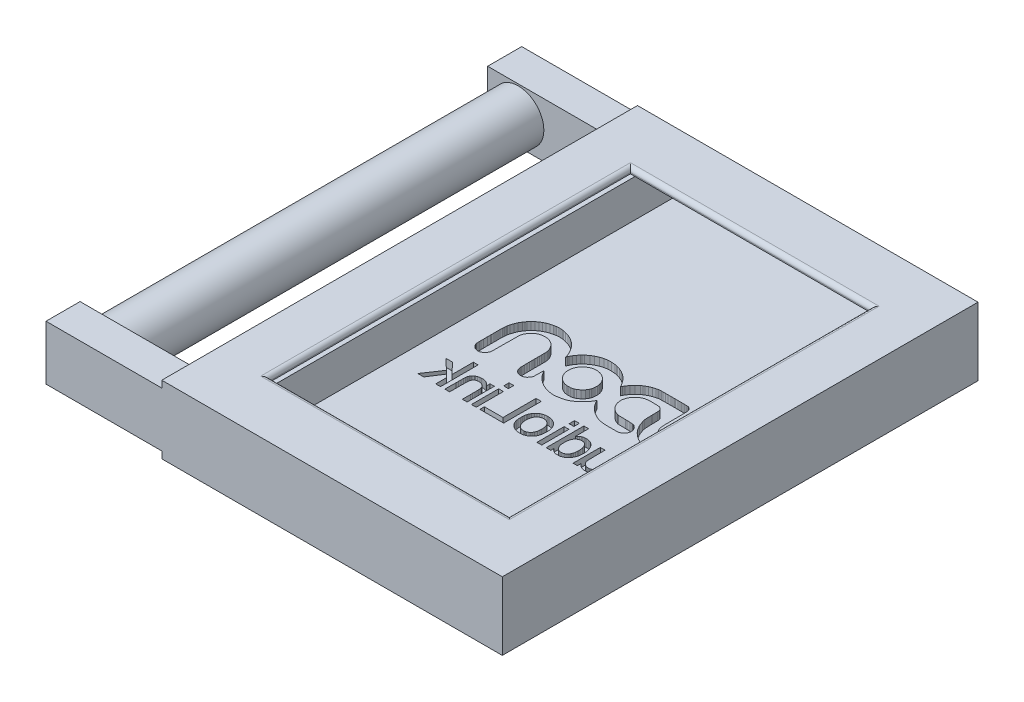
SolidWorks part; units mm, degrees
material "6061 Alloy"
ref_plane "Front" through (0, 0, 0) normal (0, 0, 1) x (1, 0, 0)
ref_plane "Top" through (0, 0, 0) normal (0, 1, 0) x (1, 0, 0)
ref_plane "Right" through (0, 0, 0) normal (1, 0, 0) x (0, 0, -1)
sketch "Sketch1" plane through (0, 0, 0) normal (0, 1, 0) x (1, 0, 0)
  line L1 (-100, -139.7) -> (100, -139.7)
  line L2 (-100, -139.7) -> (-100, 139.7)
  line L3 (-100, 139.7) -> (100, 139.7)
  line L4 (100, -139.7) -> (100, 139.7)
  line L5 (-100, -139.7) -> (100, 139.7) construction
  line L6 (-100, 139.7) -> (100, -139.7) construction
  point P0 (0, 0)
  dimension "D1" = 279.4
  dimension "D2" = 200
extrude "Boss-Extrude1" add sketch "Sketch1" along normal mid plane 40
sketch "Sketch2" plane through (0, 0, 0) normal (0, 1, 0) x (1, 0, 0)
  line L1 (-100, 139.7) -> (-168, 139.7)
  line L2 (-100, 139.7) -> (-100, 119.7)
  line L3 (-100, 119.7) -> (-168, 119.7)
  line L4 (-168, 139.7) -> (-168, 119.7)
  dimension "D1" = 68
  dimension "D2" = 20
extrude "Boss-Extrude2" add sketch "Sketch2" along normal mid plane 32
sketch "Sketch3" plane through (0, 0, 0) normal (0, 0, 1) x (1, 0, 0)
  circle A0 centre (-150, 0) radius 15
  point P2 (0, 0)
  dimension "D1" = 30
  dimension "D2" = 150
extrude "Boss-Extrude3" add sketch "Sketch3" against normal up to surface (119.7 mm away) up to face at (-134, 0, -119.7)
mirror "Mirror1" about plane through (0, 0, 0) normal (0, 0, 1) of "Boss-Extrude2", "Boss-Extrude3"
sketch "Sketch4" plane through (0, 20, 0) normal (0, 1, 0) x (1, 0, 0)
  line L1 (-70.485, -106.045) -> (70.485, -106.045)
  line L2 (-70.485, -106.045) -> (-70.485, 106.045)
  line L3 (-70.485, 106.045) -> (70.485, 106.045)
  line L4 (70.485, -106.045) -> (70.485, 106.045)
  line L5 (-70.485, -106.045) -> (70.485, 106.045) construction
  line L6 (-70.485, 106.045) -> (70.485, -106.045) construction
  point P0 (0, 0)
  dimension "D1" = 212.09
  dimension "D2" = 140.97
extrude "Cut-Extrude1" cut sketch "Sketch4" against normal blind 6.35
sketch "Sketch5" plane through (0, 0, 139.7) normal (0, 0, 1) x (1, 0, 0)
  line L0 (70.485, 13.65) -> (70.485, 20) construction
  line L1 (-87.249, 16.825) -> (87.249, 16.825)
  line L2 (-87.249, 16.825) -> (-87.249, 8.443)
  line L3 (-87.249, 8.443) -> (87.249, 8.443)
  line L4 (87.249, 16.825) -> (87.249, 8.443)
  line L5 (-87.249, 16.825) -> (87.249, 8.443) construction
  line L6 (-87.249, 8.443) -> (87.249, 16.825) construction
  line L7 (-70.485, 13.65) -> (-70.485, 20) construction
  line L8 (70.485, 13.65) -> (70.485, 20) construction
  line L9 (-70.485, 13.65) -> (-70.485, 20) construction
  line L10 (-100, 20) -> (100, 20) construction
  point P0 (0, 12.634)
  dimension "D1" = 8.382
  dimension "D2" = 3.175
  dimension "D3" = 16.764
  dimension "D4" = 16.764
extrude "Cut-Extrude2" cut sketch "Sketch5" along normal offset from surface (262.509 mm away) 16.764 from surface up to face at (0, 16.825, 106.045) offset beyond the face yes starting at face at (-67, 0, -139.7)
fillet "Fillet1" radius 2.54 4 edges at (0, 20, 106.045) (70.485, 20, 0) (-70.485, 20, 0) (0, 20, -106.045)
sketch "Sketch6" plane through (0, 0, -139.7) normal (0, 0, -1) x (-1, 0, 0)
  line L0 (87.249, 8.443) -> (-87.249, 8.443) construction
  line L1 (-76.2, -13.65) -> (76.2, -13.65)
  line L2 (-76.2, -13.65) -> (-76.2, 8.443)
  line L3 (-76.2, 8.443) -> (76.2, 8.443)
  line L4 (76.2, -13.65) -> (76.2, 8.443)
  line L5 (-76.2, -13.65) -> (76.2, 8.443) construction
  line L6 (-76.2, 8.443) -> (76.2, -13.65) construction
  line L7 (-100, -20) -> (100, -20) construction
  point P0 (0, -2.6035)
  point P7 (0, 0)
  dimension "D1" = 152.4
  dimension "D2" = 6.35
extrude "Cut-Extrude3" cut sketch "Sketch6" against normal up to surface (262.509 mm away) up to face at (0, 12.634, 122.809)
sketch "Sketch9" plane through (0, -20, 0) normal (0, -1, 0) x (1, 0, 0)
  line L0 (47.93, -1.8124) -> (48.8593, -2.019)
  line L1 (48.8593, -2.019) -> (50.5205, -2.4998)
  line L2 (50.5205, -2.4998) -> (52.0185, -3.112)
  line L3 (52.0185, -3.112) -> (53.4733, -3.9044)
  line L4 (53.4733, -3.9044) -> (54.222, -4.3835)
  line L5 (54.222, -4.3835) -> (54.8334, -4.8153)
  line L6 (54.8334, -4.8153) -> (56.0096, -5.784)
  line L7 (56.0096, -5.784) -> (57.1117, -6.8762)
  line L8 (57.1117, -6.8762) -> (58.1253, -8.0714)
  line L9 (58.1253, -8.0714) -> (59.0359, -9.3494)
  line L10 (59.0359, -9.3494) -> (59.829, -10.6898)
  line L11 (59.829, -10.6898) -> (60.49, -12.0723)
  line L12 (60.49, -12.0723) -> (61.0045, -13.4765)
  line L13 (61.0045, -13.4765) -> (61.2023, -14.1804)
  line L14 (61.2023, -14.1804) -> (61.4, -15.0085)
  line L15 (61.4, -15.0085) -> (61.6145, -16.1928)
  line L16 (61.6145, -16.1928) -> (61.7109, -17.0783)
  line L17 (61.7109, -17.0783) -> (61.7768, -18.1482)
  line L18 (61.7768, -18.1482) -> (61.8178, -19.4948)
  line L19 (61.8178, -19.4948) -> (61.8396, -21.2101)
  line L20 (61.8396, -21.2101) -> (61.8467, -22.7941)
  line L21 (61.8467, -22.7941) -> (61.8484, -24.0134)
  line L22 (61.8484, -24.0134) -> (61.8486, -24.6763)
  line L23 (61.8486, -24.6763) -> (61.8486, -25.2604)
  line L24 (61.8486, -25.2604) -> (61.8482, -26.327)
  line L25 (61.8482, -26.327) -> (61.846, -27.691)
  line L26 (61.846, -27.691) -> (61.8385, -29.1187)
  line L27 (61.8385, -29.1187) -> (61.8233, -30.1692)
  line L28 (61.8233, -30.1692) -> (61.798, -30.9181)
  line L29 (61.798, -30.9181) -> (61.7599, -31.4412)
  line L30 (61.7599, -31.4412) -> (61.6732, -31.9679)
  line L31 (61.6732, -31.9679) -> (61.5921, -32.2575)
  line L32 (61.5921, -32.2575) -> (61.4441, -32.651)
  line L33 (61.4441, -32.651) -> (61.0089, -33.4052)
  line L34 (61.0089, -33.4052) -> (60.4202, -34.0791)
  line L35 (60.4202, -34.0791) -> (59.7166, -34.6283)
  line L36 (59.7166, -34.6283) -> (59.3337, -34.8425)
  line L37 (59.3337, -34.8425) -> (58.9346, -35.0064)
  line L38 (58.9346, -35.0064) -> (58.0614, -35.1964)
  line L39 (58.0614, -35.1964) -> (57.1488, -35.2022)
  line L40 (57.1488, -35.2022) -> (56.2694, -35.0232)
  line L41 (56.2694, -35.0232) -> (55.8648, -34.8643)
  line L42 (55.8648, -34.8643) -> (55.3692, -34.5995)
  line L43 (55.3692, -34.5995) -> (54.5302, -33.9483)
  line L44 (54.5302, -33.9483) -> (53.8984, -33.1408)
  line L45 (53.8984, -33.1408) -> (53.4792, -32.1837)
  line L46 (53.4792, -32.1837) -> (53.351, -31.6514)
  line L47 (53.351, -31.6514) -> (53.3349, -31.5347)
  line L48 (53.3349, -31.5347) -> (53.3054, -31.1451)
  line L49 (53.3054, -31.1451) -> (53.2796, -30.5535)
  line L50 (53.2796, -30.5535) -> (53.2577, -29.7676)
  line L51 (53.2577, -29.7676) -> (53.2397, -28.795)
  line L52 (53.2397, -28.795) -> (53.2258, -27.6434)
  line L53 (53.2258, -27.6434) -> (53.2161, -26.3204)
  line L54 (53.2161, -26.3204) -> (53.2108, -24.8337)
  line L55 (53.2108, -24.8337) -> (53.2099, -24.0314)
  line L56 (53.2099, -24.0314) -> (53.2069, -22.5476)
  line L57 (53.2069, -22.5476) -> (53.1942, -20.5567)
  line L58 (53.1942, -20.5567) -> (53.1807, -19.4123)
  line L59 (53.1807, -19.4123) -> (53.1636, -18.4351)
  line L60 (53.1636, -18.4351) -> (53.1432, -17.6434)
  line L61 (53.1432, -17.6434) -> (53.1198, -17.055)
  line L62 (53.1198, -17.055) -> (53.0937, -16.6882)
  line L63 (53.0937, -16.6882) -> (53.0797, -16.5934)
  line L64 (53.0797, -16.5934) -> (52.8926, -15.8966)
  line L65 (52.8926, -15.8966) -> (52.3521, -14.5891)
  line L66 (52.3521, -14.5891) -> (51.6095, -13.4123)
  line L67 (51.6095, -13.4123) -> (50.6885, -12.385)
  line L68 (50.6885, -12.385) -> (49.6127, -11.5261)
  line L69 (49.6127, -11.5261) -> (48.4057, -10.8544)
  line L70 (48.4057, -10.8544) -> (47.0912, -10.3889)
  line L71 (47.0912, -10.3889) -> (45.6927, -10.1483)
  line L72 (45.6927, -10.1483) -> (44.9694, -10.1183)
  line L73 (44.9694, -10.1183) -> (43.9951, -10.1684)
  line L74 (43.9951, -10.1684) -> (42.185, -10.5837)
  line L75 (42.185, -10.5837) -> (41.2769, -10.9654)
  line L76 (41.2769, -10.9654) -> (40.8053, -11.229)
  line L77 (40.8053, -11.229) -> (39.795, -11.9878)
  line L78 (39.795, -11.9878) -> (38.8185, -12.936)
  line L79 (38.8185, -12.936) -> (38.0234, -13.93)
  line L80 (38.0234, -13.93) -> (37.7401, -14.3995)
  line L81 (37.7401, -14.3995) -> (37.5607, -14.7386)
  line L82 (37.5607, -14.7386) -> (37.2712, -15.3057)
  line L83 (37.2712, -15.3057) -> (37.0622, -15.844)
  line L84 (37.0622, -15.844) -> (36.9192, -16.4977)
  line L85 (36.9192, -16.4977) -> (36.8279, -17.4103)
  line L86 (36.8279, -17.4103) -> (36.7846, -18.3514)
  line L87 (36.7846, -18.3514) -> (36.7643, -19.1346)
  line L88 (36.7643, -19.1346) -> (36.7489, -20.0635)
  line L89 (36.7489, -20.0635) -> (36.7365, -21.1561)
  line L90 (36.7365, -21.1561) -> (36.7253, -22.4303)
  line L91 (36.7253, -22.4303) -> (36.7135, -23.9041)
  line L92 (36.7135, -23.9041) -> (36.7068, -24.7214)
  line L93 (36.7068, -24.7214) -> (36.7002, -25.5284)
  line L94 (36.7002, -25.5284) -> (36.6881, -26.9863)
  line L95 (36.6881, -26.9863) -> (36.6766, -28.2491)
  line L96 (36.6766, -28.2491) -> (36.664, -29.3326)
  line L97 (36.664, -29.3326) -> (36.6488, -30.2526)
  line L98 (36.6488, -30.2526) -> (36.6297, -31.0248)
  line L99 (36.6297, -31.0248) -> (36.5902, -31.9403)
  line L100 (36.5902, -31.9403) -> (36.5095, -32.7906)
  line L101 (36.5095, -32.7906) -> (36.3858, -33.3329)
  line L102 (36.3858, -33.3329) -> (36.0936, -33.8445)
  line L103 (36.0936, -33.8445) -> (35.8102, -34.1679)
  line L104 (35.8102, -34.1679) -> (35.3632, -34.5848)
  line L105 (35.3632, -34.5848) -> (34.8735, -34.9207)
  line L106 (34.8735, -34.9207) -> (34.6857, -35.0125)
  line L107 (34.6857, -35.0125) -> (34.2701, -35.1085)
  line L108 (34.2701, -35.1085) -> (33.7539, -35.1494)
  line L109 (33.7539, -35.1494) -> (32.9267, -35.1756)
  line L110 (32.9267, -35.1756) -> (32.0403, -35.1876)
  line L111 (32.0403, -35.1876) -> (31.2987, -35.1927)
  line L112 (31.2987, -35.1927) -> (30.4215, -35.196)
  line L113 (30.4215, -35.196) -> (29.3959, -35.1979)
  line L114 (29.3959, -35.1979) -> (28.2091, -35.1987)
  line L115 (28.2091, -35.1987) -> (26.8482, -35.1989)
  line L116 (26.8482, -35.1989) -> (26.0985, -35.1989)
  line L117 (26.0985, -35.1989) -> (25.4237, -35.1989)
  line L118 (25.4237, -35.1989) -> (24.1823, -35.1982)
  line L119 (24.1823, -35.1982) -> (22.573, -35.1954)
  line L120 (22.573, -35.1954) -> (20.8496, -35.1874)
  line L121 (20.8496, -35.1874) -> (19.5398, -35.1726)
  line L122 (19.5398, -35.1726) -> (18.5682, -35.1492)
  line L123 (18.5682, -35.1492) -> (17.8592, -35.1155)
  line L124 (17.8592, -35.1155) -> (17.1232, -35.0417)
  line L125 (17.1232, -35.0417) -> (16.7409, -34.9742)
  line L126 (16.7409, -34.9742) -> (15.8881, -34.7797)
  line L127 (15.8881, -34.7797) -> (14.2327, -34.2776)
  line L128 (14.2327, -34.2776) -> (12.6521, -33.628)
  line L129 (12.6521, -33.628) -> (11.1562, -32.8348)
  line L130 (11.1562, -32.8348) -> (10.443, -32.3856)
  line L131 (10.443, -32.3856) -> (9.6232, -31.7926)
  line L132 (9.6232, -31.7926) -> (8.0064, -30.3585)
  line L133 (8.0064, -30.3585) -> (6.5288, -28.7146)
  line L134 (6.5288, -28.7146) -> (5.3208, -27.006)
  line L135 (5.3208, -27.006) -> (4.8587, -26.1729)
  line L136 (4.8587, -26.1729) -> (4.4117, -25.2748)
  line L137 (4.4117, -25.2748) -> (3.998, -26.0686)
  line L138 (3.998, -26.0686) -> (3.5333, -26.9017)
  line L139 (3.5333, -26.9017) -> (2.4731, -28.475)
  line L140 (2.4731, -28.475) -> (1.2523, -29.914)
  line L141 (1.2523, -29.914) -> (-0.1132, -31.2064)
  line L142 (-0.1132, -31.2064) -> (-1.607, -32.34)
  line L143 (-1.607, -32.34) -> (-3.2132, -33.3026)
  line L144 (-3.2132, -33.3026) -> (-4.9154, -34.0818)
  line L145 (-4.9154, -34.0818) -> (-6.6976, -34.6655)
  line L146 (-6.6976, -34.6655) -> (-7.6137, -34.8801)
  line L147 (-7.6137, -34.8801) -> (-8.6686, -35.0616)
  line L148 (-8.6686, -35.0616) -> (-10.7713, -35.2252)
  line L149 (-10.7713, -35.2252) -> (-12.8491, -35.1279)
  line L150 (-12.8491, -35.1279) -> (-14.8833, -34.7755)
  line L151 (-14.8833, -34.7755) -> (-16.8553, -34.1736)
  line L152 (-16.8553, -34.1736) -> (-18.7463, -33.3279)
  line L153 (-18.7463, -33.3279) -> (-20.5378, -32.2442)
  line L154 (-20.5378, -32.2442) -> (-22.2109, -30.9281)
  line L155 (-22.2109, -30.9281) -> (-22.9973, -30.1847)
  line L156 (-22.9973, -30.1847) -> (-23.5248, -29.6247)
  line L157 (-23.5248, -29.6247) -> (-24.5397, -28.3737)
  line L158 (-24.5397, -28.3737) -> (-25.4499, -27.0237)
  line L159 (-25.4499, -27.0237) -> (-26.1944, -25.6654)
  line L160 (-26.1944, -25.6654) -> (-26.4854, -25.0115)
  line L161 (-26.4854, -25.0115) -> (-26.7632, -24.328)
  line L162 (-26.7632, -24.328) -> (-27.0924, -25.382)
  line L163 (-27.0924, -25.382) -> (-27.4778, -26.465)
  line L164 (-27.4778, -26.465) -> (-28.506, -28.5948)
  line L165 (-28.506, -28.5948) -> (-29.8176, -30.5858)
  line L166 (-29.8176, -30.5858) -> (-31.3414, -32.3296)
  line L167 (-31.3414, -32.3296) -> (-32.1605, -33.075)
  line L168 (-32.1605, -33.075) -> (-33.1539, -33.8619)
  line L169 (-33.1539, -33.8619) -> (-35.1274, -35.1509)
  line L170 (-35.1274, -35.1509) -> (-37.1834, -36.1065)
  line L171 (-37.1834, -36.1065) -> (-39.442, -36.7846)
  line L172 (-39.442, -36.7846) -> (-40.6848, -37.0371)
  line L173 (-40.6848, -37.0371) -> (-41.3523, -37.1437)
  line L174 (-41.3523, -37.1437) -> (-42.5862, -37.2657)
  line L175 (-42.5862, -37.2657) -> (-43.7685, -37.2661)
  line L176 (-43.7685, -37.2661) -> (-44.9993, -37.1451)
  line L177 (-44.9993, -37.1451) -> (-45.6641, -37.0391)
  line L178 (-45.6641, -37.0391) -> (-46.5297, -36.868)
  line L179 (-46.5297, -36.868) -> (-48.1852, -36.4278)
  line L180 (-48.1852, -36.4278) -> (-49.7428, -35.8549)
  line L181 (-49.7428, -35.8549) -> (-51.2063, -35.1471)
  line L182 (-51.2063, -35.1471) -> (-52.5794, -34.302)
  line L183 (-52.5794, -34.302) -> (-53.8658, -33.3174)
  line L184 (-53.8658, -33.3174) -> (-55.0694, -32.1909)
  line L185 (-55.0694, -32.1909) -> (-56.1937, -30.9202)
  line L186 (-56.1937, -30.9202) -> (-56.7274, -30.2301)
  line L187 (-56.7274, -30.2301) -> (-57.2616, -29.4642)
  line L188 (-57.2616, -29.4642) -> (-58.1905, -27.8525)
  line L189 (-58.1905, -27.8525) -> (-58.9425, -26.1127)
  line L190 (-58.9425, -26.1127) -> (-59.5287, -24.2193)
  line L191 (-59.5287, -24.2193) -> (-59.7631, -23.2069)
  line L192 (-59.7631, -23.2069) -> (-59.8639, -22.7055)
  line L193 (-59.8639, -22.7055) -> (-59.9693, -21.9562)
  line L194 (-59.9693, -21.9562) -> (-60.0143, -21.2913)
  line L195 (-60.0143, -21.2913) -> (-60.0433, -20.3602)
  line L196 (-60.0433, -20.3602) -> (-60.0598, -19.0481)
  line L197 (-60.0598, -19.0481) -> (-60.0662, -17.7451)
  line L198 (-60.0662, -17.7451) -> (-60.0684, -16.6976)
  line L199 (-60.0684, -16.6976) -> (-60.0695, -15.4904)
  line L200 (-60.0695, -15.4904) -> (-60.0699, -14.109)
  line L201 (-60.0699, -14.109) -> (-60.07, -13.3486)
  line L202 (-60.07, -13.3486) -> (-60.0679, -11.6508)
  line L203 (-60.0679, -11.6508) -> (-60.057, -9.3283)
  line L204 (-60.057, -9.3283) -> (-60.0452, -7.9785)
  line L205 (-60.0452, -7.9785) -> (-60.0302, -6.8266)
  line L206 (-60.0302, -6.8266) -> (-60.0125, -5.9063)
  line L207 (-60.0125, -5.9063) -> (-59.9926, -5.2512)
  line L208 (-59.9926, -5.2512) -> (-59.9708, -4.8951)
  line L209 (-59.9708, -4.8951) -> (-59.9593, -4.8396)
  line L210 (-59.9593, -4.8396) -> (-59.9043, -4.756)
  line L211 (-59.9043, -4.756) -> (-59.7656, -4.4437)
  line L212 (-59.7656, -4.4437) -> (-59.699, -4.2534)
  line L213 (-59.699, -4.2534) -> (-59.6021, -4.0237)
  line L214 (-59.6021, -4.0237) -> (-59.2623, -3.4944)
  line L215 (-59.2623, -3.4944) -> (-58.5336, -2.6951)
  line L216 (-58.5336, -2.6951) -> (-58.0151, -2.2908)
  line L217 (-58.0151, -2.2908) -> (-57.7273, -2.1311)
  line L218 (-57.7273, -2.1311) -> (-57.055, -1.8689)
  line L219 (-57.055, -1.8689) -> (-56.3263, -1.7002)
  line L220 (-56.3263, -1.7002) -> (-55.6278, -1.6448)
  line L221 (-55.6278, -1.6448) -> (-55.3171, -1.666)
  line L222 (-55.3171, -1.666) -> (-54.7785, -1.7767)
  line L223 (-54.7785, -1.7767) -> (-53.7585, -2.2139)
  line L224 (-53.7585, -2.2139) -> (-52.8596, -2.9046)
  line L225 (-52.8596, -2.9046) -> (-52.136, -3.807)
  line L226 (-52.136, -3.807) -> (-51.8568, -4.3246)
  line L227 (-51.8568, -4.3246) -> (-51.4985, -5.0999)
  line L228 (-51.4985, -5.0999) -> (-51.4312, -13.6724)
  line L229 (-51.4312, -13.6724) -> (-51.4252, -14.4369)
  line L230 (-51.4252, -14.4369) -> (-51.4139, -15.8277)
  line L231 (-51.4139, -15.8277) -> (-51.4034, -17.0448)
  line L232 (-51.4034, -17.0448) -> (-51.393, -18.101)
  line L233 (-51.393, -18.101) -> (-51.3824, -19.0094)
  line L234 (-51.3824, -19.0094) -> (-51.371, -19.7826)
  line L235 (-51.371, -19.7826) -> (-51.3516, -20.7173)
  line L236 (-51.3516, -20.7173) -> (-51.3186, -21.6106)
  line L237 (-51.3186, -21.6106) -> (-51.2741, -22.1949)
  line L238 (-51.2741, -22.1949) -> (-51.1775, -22.7169)
  line L239 (-51.1775, -22.7169) -> (-51.0877, -22.9784)
  line L240 (-51.0877, -22.9784) -> (-50.776, -23.7156)
  line L241 (-50.776, -23.7156) -> (-49.9983, -25.0764)
  line L242 (-49.9983, -25.0764) -> (-49.0459, -26.2477)
  line L243 (-49.0459, -26.2477) -> (-47.9559, -27.1837)
  line L244 (-47.9559, -27.1837) -> (-47.371, -27.5492)
  line L245 (-47.371, -27.5492) -> (-46.8306, -27.8335)
  line L246 (-46.8306, -27.8335) -> (-45.853, -28.2463)
  line L247 (-45.853, -28.2463) -> (-44.8852, -28.4825)
  line L248 (-44.8852, -28.4825) -> (-43.7739, -28.5794)
  line L249 (-43.7739, -28.5794) -> (-43.1165, -28.5874)
  line L250 (-43.1165, -28.5874) -> (-42.6016, -28.5831)
  line L251 (-42.6016, -28.5831) -> (-41.8473, -28.5534)
  line L252 (-41.8473, -28.5534) -> (-41.2968, -28.4714)
  line L253 (-41.2968, -28.4714) -> (-40.7543, -28.3077)
  line L254 (-40.7543, -28.3077) -> (-40.4247, -28.186)
  line L255 (-40.4247, -28.186) -> (-39.9657, -27.9967)
  line L256 (-39.9657, -27.9967) -> (-39.0406, -27.5409)
  line L257 (-39.0406, -27.5409) -> (-38.6885, -27.3306)
  line L258 (-38.6885, -27.3306) -> (-38.2703, -27.0276)
  line L259 (-38.2703, -27.0276) -> (-37.4493, -26.2898)
  line L260 (-37.4493, -26.2898) -> (-36.6972, -25.4315)
  line L261 (-36.6972, -25.4315) -> (-36.0723, -24.5191)
  line L262 (-36.0723, -24.5191) -> (-35.8257, -24.0634)
  line L263 (-35.8257, -24.0634) -> (-35.5228, -23.4356)
  line L264 (-35.5228, -23.4356) -> (-35.2091, -22.5816)
  line L265 (-35.2091, -22.5816) -> (-35.0772, -21.8826)
  line L266 (-35.0772, -21.8826) -> (-34.9942, -20.9297)
  line L267 (-34.9942, -20.9297) -> (-34.9571, -19.9706)
  line L268 (-34.9571, -19.9706) -> (-34.9417, -19.1848)
  line L269 (-34.9417, -19.1848) -> (-34.9322, -18.2629)
  line L270 (-34.9322, -18.2629) -> (-34.9272, -17.1889)
  line L271 (-34.9272, -17.1889) -> (-34.9253, -15.9467)
  line L272 (-34.9253, -15.9467) -> (-34.925, -14.52)
  line L273 (-34.925, -14.52) -> (-34.925, -13.7326)
  line L274 (-34.925, -13.7326) -> (-34.9244, -12.8119)
  line L275 (-34.9244, -12.8119) -> (-34.9199, -11.1176)
  line L276 (-34.9199, -11.1176) -> (-34.911, -9.6236)
  line L277 (-34.911, -9.6236) -> (-34.8978, -8.335)
  line L278 (-34.8978, -8.335) -> (-34.8803, -7.2571)
  line L279 (-34.8803, -7.2571) -> (-34.8587, -6.3951)
  line L280 (-34.8587, -6.3951) -> (-34.833, -5.7541)
  line L281 (-34.833, -5.7541) -> (-34.8033, -5.3394)
  line L282 (-34.8033, -5.3394) -> (-34.787, -5.2185)
  line L283 (-34.787, -5.2185) -> (-34.6999, -4.8323)
  line L284 (-34.6999, -4.8323) -> (-34.4399, -4.1124)
  line L285 (-34.4399, -4.1124) -> (-34.0739, -3.4695)
  line L286 (-34.0739, -3.4695) -> (-33.6116, -2.9118)
  line L287 (-33.6116, -2.9118) -> (-33.063, -2.4477)
  line L288 (-33.063, -2.4477) -> (-32.4378, -2.0856)
  line L289 (-32.4378, -2.0856) -> (-31.746, -1.8338)
  line L290 (-31.746, -1.8338) -> (-30.9973, -1.7005)
  line L291 (-30.9973, -1.7005) -> (-30.6047, -1.681)
  line L292 (-30.6047, -1.681) -> (-29.981, -1.7185)
  line L293 (-29.981, -1.7185) -> (-28.8386, -2.046)
  line L294 (-28.8386, -2.046) -> (-27.851, -2.7004)
  line L295 (-27.851, -2.7004) -> (-27.0358, -3.6702)
  line L296 (-27.0358, -3.6702) -> (-26.6984, -4.2697)
  line L297 (-26.6984, -4.2697) -> (-26.585, -4.5073)
  line L298 (-26.585, -4.5073) -> (-26.4362, -4.9681)
  line L299 (-26.4362, -4.9681) -> (-26.3751, -5.4722)
  line L300 (-26.3751, -5.4722) -> (-26.3502, -5.9652)
  line L301 (-26.3502, -5.9652) -> (-26.3328, -6.6345)
  line L302 (-26.3328, -6.6345) -> (-26.3184, -7.5234)
  line L303 (-26.3184, -7.5234) -> (-26.3109, -8.0637)
  line L304 (-26.3109, -8.0637) -> (-26.2689, -11.1546)
  line L305 (-26.2689, -11.1546) -> (-25.7104, -10.1744)
  line L306 (-25.7104, -10.1744) -> (-25.2365, -9.3917)
  line L307 (-25.2365, -9.3917) -> (-24.177, -7.917)
  line L308 (-24.177, -7.917) -> (-22.9796, -6.5718)
  line L309 (-22.9796, -6.5718) -> (-21.6581, -5.3662)
  line L310 (-21.6581, -5.3662) -> (-20.2262, -4.3101)
  line L311 (-20.2262, -4.3101) -> (-18.6974, -3.4138)
  line L312 (-18.6974, -3.4138) -> (-17.0854, -2.6873)
  line L313 (-17.0854, -2.6873) -> (-15.404, -2.1406)
  line L314 (-15.404, -2.1406) -> (-14.5415, -1.9379)
  line L315 (-14.5415, -1.9379) -> (-14.0986, -1.847)
  line L316 (-14.0986, -1.847) -> (-13.2307, -1.6695)
  line L317 (-13.2307, -1.6695) -> (-12.9126, -1.6047)
  line L318 (-12.9126, -1.6047) -> (-12.466, -1.5337)
  line L319 (-12.466, -1.5337) -> (-11.4389, -1.475)
  line L320 (-11.4389, -1.475) -> (-9.655, -1.5789)
  line L321 (-9.655, -1.5789) -> (-7.0806, -2.0304)
  line L322 (-7.0806, -2.0304) -> (-5.2179, -2.5662)
  line L323 (-5.2179, -2.5662) -> (-4.1006, -3.001)
  line L324 (-4.1006, -3.001) -> (-3.5977, -3.2385)
  line L325 (-3.5977, -3.2385) -> (-2.4454, -3.8854)
  line L326 (-2.4454, -3.8854) -> (-0.2515, -5.484)
  line L327 (-0.2515, -5.484) -> (1.7045, -7.4005)
  line L328 (1.7045, -7.4005) -> (3.3142, -9.5288)
  line L329 (3.3142, -9.5288) -> (3.9552, -10.6392)
  line L330 (3.9552, -10.6392) -> (4.3904, -11.4794)
  line L331 (4.3904, -11.4794) -> (4.9413, -10.4279)
  line L332 (4.9413, -10.4279) -> (5.3263, -9.7401)
  line L333 (5.3263, -9.7401) -> (6.2161, -8.4126)
  line L334 (6.2161, -8.4126) -> (7.2502, -7.1614)
  line L335 (7.2502, -7.1614) -> (8.4106, -6.0016)
  line L336 (8.4106, -6.0016) -> (9.6792, -4.9484)
  line L337 (9.6792, -4.9484) -> (11.0377, -4.0168)
  line L338 (11.0377, -4.0168) -> (12.468, -3.2219)
  line L339 (12.468, -3.2219) -> (13.9519, -2.5787)
  line L340 (13.9519, -2.5787) -> (14.7084, -2.3187)
  line L341 (14.7084, -2.3187) -> (15.5331, -2.0749)
  line L342 (15.5331, -2.0749) -> (17.1024, -1.7339)
  line L343 (17.1024, -1.7339) -> (18.4035, -1.5869)
  line L344 (18.4035, -1.5869) -> (19.4225, -1.5316)
  line L345 (19.4225, -1.5316) -> (20.6203, -1.5047)
  line L346 (20.6203, -1.5047) -> (22.0461, -1.5013)
  line L347 (22.0461, -1.5013) -> (22.86, -1.5068)
  line L348 (22.86, -1.5068) -> (26.9875, -1.5439)
  line L349 (26.9875, -1.5439) -> (27.7793, -1.9096)
  line L350 (27.7793, -1.9096) -> (28.2315, -2.1493)
  line L351 (28.2315, -2.1493) -> (29.0123, -2.7454)
  line L352 (29.0123, -2.7454) -> (29.621, -3.4699)
  line L353 (29.621, -3.4699) -> (30.0487, -4.2897)
  line L354 (30.0487, -4.2897) -> (30.2865, -5.172)
  line L355 (30.2865, -5.172) -> (30.3255, -6.0836)
  line L356 (30.3255, -6.0836) -> (30.1568, -6.9916)
  line L357 (30.1568, -6.9916) -> (29.7716, -7.8632)
  line L358 (29.7716, -7.8632) -> (29.495, -8.2749)
  line L359 (29.495, -8.2749) -> (29.0358, -8.7861)
  line L360 (29.0358, -8.7861) -> (27.8992, -9.6272)
  line L361 (27.8992, -9.6272) -> (27.3275, -9.8789)
  line L362 (27.3275, -9.8789) -> (27.2543, -9.8968)
  line L363 (27.2543, -9.8968) -> (27.0073, -9.9317)
  line L364 (27.0073, -9.9317) -> (26.3933, -9.981)
  line L365 (26.3933, -9.981) -> (25.1434, -10.0404)
  line L366 (25.1434, -10.0404) -> (23.4327, -10.0907)
  line L367 (23.4327, -10.0907) -> (22.4155, -10.1121)
  line L368 (22.4155, -10.1121) -> (17.9705, -10.1949)
  line L369 (17.9705, -10.1949) -> (17.0207, -10.5531)
  line L370 (17.0207, -10.5531) -> (16.3324, -10.846)
  line L371 (16.3324, -10.846) -> (15.0675, -11.5821)
  line L372 (15.0675, -11.5821) -> (13.9649, -12.4963)
  line L373 (13.9649, -12.4963) -> (13.0414, -13.5613)
  line L374 (13.0414, -13.5613) -> (12.3136, -14.7502)
  line L375 (12.3136, -14.7502) -> (11.7978, -16.0359)
  line L376 (11.7978, -16.0359) -> (11.5108, -17.3913)
  line L377 (11.5108, -17.3913) -> (11.4692, -18.7893)
  line L378 (11.4692, -18.7893) -> (11.5455, -19.4959)
  line L379 (11.5455, -19.4959) -> (11.6767, -20.1945)
  line L380 (11.6767, -20.1945) -> (12.0623, -21.4564)
  line L381 (12.0623, -21.4564) -> (12.6362, -22.5846)
  line L382 (12.6362, -22.5846) -> (13.4271, -23.6357)
  line L383 (13.4271, -23.6357) -> (13.9129, -24.1499)
  line L384 (13.9129, -24.1499) -> (14.2939, -24.5126)
  line L385 (14.2939, -24.5126) -> (15.0462, -25.1282)
  line L386 (15.0462, -25.1282) -> (16.2354, -25.8314)
  line L387 (16.2354, -25.8314) -> (17.1352, -26.1956)
  line L388 (17.1352, -26.1956) -> (17.6372, -26.3521)
  line L389 (17.6372, -26.3521) -> (18.7495, -26.5798)
  line L390 (18.7495, -26.5798) -> (20.1313, -26.7051)
  line L391 (20.1313, -26.7051) -> (21.4348, -26.7401)
  line L392 (21.4348, -26.7401) -> (22.4663, -26.7384)
  line L393 (22.4663, -26.7384) -> (23.0378, -26.7308)
  line L394 (23.0378, -26.7308) -> (23.5826, -26.7212)
  line L395 (23.5826, -26.7212) -> (24.4877, -26.6984)
  line L396 (24.4877, -26.6984) -> (25.1826, -26.6629)
  line L397 (25.1826, -26.6629) -> (25.7101, -26.6053)
  line L398 (25.7101, -26.6053) -> (26.2808, -26.4567)
  line L399 (26.2808, -26.4567) -> (26.8544, -26.0928)
  line L400 (26.8544, -26.0928) -> (27.1571, -25.8185)
  line L401 (27.1571, -25.8185) -> (27.4357, -25.5494)
  line L402 (27.4357, -25.5494) -> (27.7976, -24.9893)
  line L403 (27.7976, -24.9893) -> (27.9422, -24.292)
  line L404 (27.9422, -24.292) -> (27.9993, -23.5723)
  line L405 (27.9993, -23.5723) -> (28.0381, -22.5723)
  line L406 (28.0381, -22.5723) -> (28.0698, -21.2265)
  line L407 (28.0698, -21.2265) -> (28.0865, -20.4034)
  line L408 (28.0865, -20.4034) -> (28.0982, -19.8547)
  line L409 (28.0982, -19.8547) -> (28.1231, -18.861)
  line L410 (28.1231, -18.861) -> (28.1652, -17.6148)
  line L411 (28.1652, -17.6148) -> (28.2323, -16.3682)
  line L412 (28.2323, -16.3682) -> (28.3151, -15.5383)
  line L413 (28.3151, -15.5383) -> (28.3635, -15.2599)
  line L414 (28.3635, -15.2599) -> (28.7437, -13.783)
  line L415 (28.7437, -13.783) -> (29.837, -11.001)
  line L416 (29.837, -11.001) -> (31.3485, -8.4905)
  line L417 (31.3485, -8.4905) -> (32.7383, -6.8163)
  line L418 (32.7383, -6.8163) -> (33.7796, -5.8114)
  line L419 (33.7796, -5.8114) -> (34.3332, -5.3448)
  line L420 (34.3332, -5.3448) -> (35.1932, -4.6885)
  line L421 (35.1932, -4.6885) -> (36.9311, -3.5871)
  line L422 (36.9311, -3.5871) -> (38.7596, -2.7366)
  line L423 (38.7596, -2.7366) -> (40.7584, -2.0999)
  line L424 (40.7584, -2.0999) -> (41.8465, -1.85)
  line L425 (41.8465, -1.85) -> (42.6782, -1.6958)
  line L426 (42.6782, -1.6958) -> (44.211, -1.5159)
  line L427 (44.211, -1.5159) -> (45.6624, -1.507)
  line L428 (45.6624, -1.507) -> (47.1435, -1.6682)
  line L429 (47.1435, -1.6682) -> (47.93, -1.8124)
  line L430 (22.479, 27.6239) -> (22.8987, 27.475)
  line L431 (22.8987, 27.475) -> (23.6208, 27.1527)
  line L432 (23.6208, 27.1527) -> (24.2551, 26.7544)
  line L433 (24.2551, 26.7544) -> (24.884, 26.2286)
  line L434 (24.884, 26.2286) -> (25.2222, 25.9016)
  line L435 (25.2222, 25.9016) -> (25.5751, 25.5248)
  line L436 (25.5751, 25.5248) -> (26.1896, 24.7175)
  line L437 (26.1896, 24.7175) -> (26.6918, 23.8219)
  line L438 (26.6918, 23.8219) -> (27.0931, 22.8177)
  line L439 (27.0931, 22.8177) -> (27.2595, 22.2686)
  line L440 (27.2595, 22.2686) -> (27.3162, 22.0251)
  line L441 (27.3162, 22.0251) -> (27.407, 21.4175)
  line L442 (27.407, 21.4175) -> (27.4863, 20.2929)
  line L443 (27.4863, 20.2929) -> (27.4858, 18.6436)
  line L444 (27.4858, 18.6436) -> (27.4058, 17.5012)
  line L445 (27.4058, 17.5012) -> (27.3146, 16.8732)
  line L446 (27.3146, 16.8732) -> (27.2577, 16.6171)
  line L447 (27.2577, 16.6171) -> (27.0032, 15.7815)
  line L448 (27.0032, 15.7815) -> (26.3203, 14.2855)
  line L449 (26.3203, 14.2855) -> (25.4256, 13.0509)
  line L450 (25.4256, 13.0509) -> (24.3438, 12.1115)
  line L451 (24.3438, 12.1115) -> (23.7403, 11.7631)
  line L452 (23.7403, 11.7631) -> (23.3338, 11.5756)
  line L453 (23.3338, 11.5756) -> (22.5586, 11.3014)
  line L454 (22.5586, 11.3014) -> (21.7685, 11.1489)
  line L455 (21.7685, 11.1489) -> (20.8854, 11.1028)
  line L456 (20.8854, 11.1028) -> (20.3844, 11.115)
  line L457 (20.3844, 11.115) -> (20.0415, 11.1329)
  line L458 (20.0415, 11.1329) -> (19.5012, 11.1873)
  line L459 (19.5012, 11.1873) -> (18.8608, 11.3595)
  line L460 (18.8608, 11.3595) -> (18.396, 11.5692)
  line L461 (18.396, 11.5692) -> (17.6424, 12.0268)
  line L462 (17.6424, 12.0268) -> (16.9802, 12.5609)
  line L463 (16.9802, 12.5609) -> (16.383, 13.1497)
  line L464 (16.383, 13.1497) -> (16.383, 9.2636)
  line L465 (16.383, 9.2636) -> (16.383, 5.3776)
  line L466 (16.383, 5.3776) -> (14.986, 5.3776)
  line L467 (14.986, 5.3776) -> (13.589, 5.3776)
  line L468 (13.589, 5.3776) -> (13.589, 16.4266)
  line L469 (13.589, 16.4266) -> (13.589, 27.4756)
  line L470 (13.589, 27.4756) -> (14.9225, 27.4756)
  line L471 (14.9225, 27.4756) -> (16.256, 27.4756)
  line L472 (16.256, 27.4756) -> (16.256, 26.592)
  line L473 (16.256, 26.592) -> (16.256, 25.7085)
  line L474 (16.256, 25.7085) -> (16.8459, 26.3391)
  line L475 (16.8459, 26.3391) -> (17.1471, 26.6263)
  line L476 (17.1471, 26.6263) -> (17.8866, 27.1671)
  line L477 (17.8866, 27.1671) -> (18.2698, 27.3803)
  line L478 (18.2698, 27.3803) -> (18.7579, 27.6029)
  line L479 (18.7579, 27.6029) -> (19.4199, 27.7687)
  line L480 (19.4199, 27.7687) -> (20.0305, 27.8114)
  line L481 (20.0305, 27.8114) -> (20.4421, 27.8237)
  line L482 (20.4421, 27.8237) -> (20.8023, 27.8296)
  line L483 (20.8023, 27.8296) -> (21.3963, 27.8185)
  line L484 (21.3963, 27.8185) -> (22.0791, 27.7338)
  line L485 (22.0791, 27.7338) -> (22.479, 27.6239)
  line L486 (0.2993, 27.6553) -> (1.0056, 27.441)
  line L487 (1.0056, 27.441) -> (2.3336, 26.7855)
  line L488 (2.3336, 26.7855) -> (3.4968, 25.8685)
  line L489 (3.4968, 25.8685) -> (4.4331, 24.7391)
  line L490 (4.4331, 24.7391) -> (4.7966, 24.1101)
  line L491 (4.7966, 24.1101) -> (5.0057, 23.6647)
  line L492 (5.0057, 23.6647) -> (5.3258, 22.7767)
  line L493 (5.3258, 22.7767) -> (5.5336, 21.806)
  line L494 (5.5336, 21.806) -> (5.6512, 20.6494)
  line L495 (5.6512, 20.6494) -> (5.683, 19.9691)
  line L496 (5.683, 19.9691) -> (5.6979, 19.1586)
  line L497 (5.6979, 19.1586) -> (5.6354, 17.7727)
  line L498 (5.6354, 17.7727) -> (5.4312, 16.5926)
  line L499 (5.4312, 16.5926) -> (5.0632, 15.4892)
  line L500 (5.0632, 15.4892) -> (4.8107, 14.9259)
  line L501 (4.8107, 14.9259) -> (4.5421, 14.4178)
  line L502 (4.5421, 14.4178) -> (3.9128, 13.5164)
  line L503 (3.9128, 13.5164) -> (3.1506, 12.7581)
  line L504 (3.1506, 12.7581) -> (2.2435, 12.1308)
  line L505 (2.2435, 12.1308) -> (1.7317, 11.8626)
  line L506 (1.7317, 11.8626) -> (1.2778, 11.656)
  line L507 (1.2778, 11.656) -> (0.4519, 11.3533)
  line L508 (0.4519, 11.3533) -> (-0.3621, 11.1771)
  line L509 (-0.3621, 11.1771) -> (-1.2809, 11.102)
  line L510 (-1.2809, 11.102) -> (-1.816, 11.0944)
  line L511 (-1.816, 11.0944) -> (-2.4479, 11.1159)
  line L512 (-2.4479, 11.1159) -> (-3.6445, 11.2798)
  line L513 (-3.6445, 11.2798) -> (-4.7465, 11.6015)
  line L514 (-4.7465, 11.6015) -> (-5.7479, 12.0769)
  line L515 (-5.7479, 12.0769) -> (-6.6427, 12.7016)
  line L516 (-6.6427, 12.7016) -> (-7.4249, 13.4715)
  line L517 (-7.4249, 13.4715) -> (-8.0885, 14.3824)
  line L518 (-8.0885, 14.3824) -> (-8.6273, 15.4301)
  line L519 (-8.6273, 15.4301) -> (-8.8481, 16.0039)
  line L520 (-8.8481, 16.0039) -> (-9.0313, 16.5932)
  line L521 (-9.0313, 16.5932) -> (-9.1787, 17.5052)
  line L522 (-9.1787, 17.5052) -> (-9.2267, 18.3941)
  line L523 (-9.2267, 18.3941) -> (-9.2446, 18.9903)
  line L524 (-9.2446, 18.9903) -> (-9.2554, 19.8309)
  line L525 (-9.2554, 19.8309) -> (-9.1924, 21.2543)
  line L526 (-9.1924, 21.2543) -> (-9.0002, 22.4368)
  line L527 (-9.0002, 22.4368) -> (-8.6586, 23.5017)
  line L528 (-8.6586, 23.5017) -> (-8.4256, 24.0285)
  line L529 (-8.4256, 24.0285) -> (-8.0707, 24.6639)
  line L530 (-8.0707, 24.6639) -> (-7.1311, 25.8054)
  line L531 (-7.1311, 25.8054) -> (-5.9292, 26.7403)
  line L532 (-5.9292, 26.7403) -> (-4.5186, 27.4269)
  line L533 (-4.5186, 27.4269) -> (-3.7516, 27.6642)
  line L534 (-3.7516, 27.6642) -> (-3.3479, 27.7427)
  line L535 (-3.3479, 27.7427) -> (-2.321, 27.8312)
  line L536 (-2.321, 27.8312) -> (-1.1768, 27.8287)
  line L537 (-1.1768, 27.8287) -> (-0.1256, 27.7357)
  line L538 (-0.1256, 27.7357) -> (0.2993, 27.6553)
  line L539 (63.5569, 26.3643) -> (63.4932, 26.1997)
  line L540 (63.4932, 26.1997) -> (63.2571, 25.5875)
  line L541 (63.2571, 25.5875) -> (62.8908, 24.6356)
  line L542 (62.8908, 24.6356) -> (62.4116, 23.3892)
  line L543 (62.4116, 23.3892) -> (61.8368, 21.8934)
  line L544 (61.8368, 21.8934) -> (61.1838, 20.1935)
  line L545 (61.1838, 20.1935) -> (60.0957, 17.3597)
  line L546 (60.0957, 17.3597) -> (59.3232, 15.3471)
  line L547 (59.3232, 15.3471) -> (55.5217, 5.4411)
  line L548 (55.5217, 5.4411) -> (53.8743, 5.4057)
  line L549 (53.8743, 5.4057) -> (53.4453, 5.3985)
  line L550 (53.4453, 5.3985) -> (52.7982, 5.4018)
  line L551 (52.7982, 5.4018) -> (52.3968, 5.4316)
  line L552 (52.3968, 5.4316) -> (52.198, 5.491)
  line L553 (52.198, 5.491) -> (52.1612, 5.5327)
  line L554 (52.1612, 5.5327) -> (52.1124, 5.6527)
  line L555 (52.1124, 5.6527) -> (51.8841, 6.2124)
  line L556 (51.8841, 6.2124) -> (51.5015, 7.1497)
  line L557 (51.5015, 7.1497) -> (50.9886, 8.4057)
  line L558 (50.9886, 8.4057) -> (50.3694, 9.9219)
  line L559 (50.3694, 9.9219) -> (49.6678, 11.6395)
  line L560 (49.6678, 11.6395) -> (48.5134, 14.4652)
  line L561 (48.5134, 14.4652) -> (46.91, 18.3897)
  line L562 (46.91, 18.3897) -> (45.7641, 21.1941)
  line L563 (45.7641, 21.1941) -> (45.0721, 22.8873)
  line L564 (45.0721, 22.8873) -> (44.4657, 24.371)
  line L565 (44.4657, 24.371) -> (43.9688, 25.5865)
  line L566 (43.9688, 25.5865) -> (43.6054, 26.475)
  line L567 (43.6054, 26.475) -> (43.3995, 26.9779)
  line L568 (43.3995, 26.9779) -> (43.3632, 27.0664)
  line L569 (43.3632, 27.0664) -> (43.19, 27.4827)
  line L570 (43.19, 27.4827) -> (44.9249, 27.4474)
  line L571 (44.9249, 27.4474) -> (46.6599, 27.4121)
  line L572 (46.6599, 27.4121) -> (47.9301, 24.0768)
  line L573 (47.9301, 24.0768) -> (49.2004, 20.7415)
  line L574 (49.2004, 20.7415) -> (53.7784, 20.7748)
  line L575 (53.7784, 20.7748) -> (58.3565, 20.8081)
  line L576 (58.3565, 20.8081) -> (59.563, 24.1414)
  line L577 (59.563, 24.1414) -> (60.7695, 27.4747)
  line L578 (60.7695, 27.4747) -> (62.3793, 27.4752)
  line L579 (62.3793, 27.4752) -> (63.9891, 27.4756)
  line L580 (63.9891, 27.4756) -> (63.5569, 26.3643)
  line L581 (-48.514, 16.4266) -> (-48.514, 5.3776)
  line L582 (-48.514, 5.3776) -> (-49.911, 5.3776)
  line L583 (-49.911, 5.3776) -> (-51.308, 5.3776)
  line L584 (-51.308, 5.3776) -> (-51.308, 11.6192)
  line L585 (-51.308, 11.6192) -> (-51.308, 17.8608)
  line L586 (-51.308, 17.8608) -> (-54.4314, 14.6672)
  line L587 (-54.4314, 14.6672) -> (-57.5549, 11.4736)
  line L588 (-57.5549, 11.4736) -> (-59.4162, 11.4765)
  line L589 (-59.4162, 11.4765) -> (-61.2775, 11.4795)
  line L590 (-61.2775, 11.4795) -> (-60.6425, 12.0714)
  line L591 (-60.6425, 12.0714) -> (-60.4652, 12.2392)
  line L592 (-60.4652, 12.2392) -> (-59.8707, 12.8119)
  line L593 (-59.8707, 12.8119) -> (-58.5678, 14.0804)
  line L594 (-58.5678, 14.0804) -> (-57.5721, 15.0561)
  line L595 (-57.5721, 15.0561) -> (-55.1367, 17.4489)
  line L596 (-55.1367, 17.4489) -> (-58.4992, 22.4622)
  line L597 (-58.4992, 22.4622) -> (-61.8616, 27.4756)
  line L598 (-61.8616, 27.4756) -> (-60.1091, 27.4712)
  line L599 (-60.1091, 27.4712) -> (-58.3565, 27.4668)
  line L600 (-58.3565, 27.4668) -> (-55.753, 23.4139)
  line L601 (-55.753, 23.4139) -> (-53.1495, 19.3611)
  line L602 (-53.1495, 19.3611) -> (-52.2288, 20.2719)
  line L603 (-52.2288, 20.2719) -> (-51.308, 21.1827)
  line L604 (-51.308, 21.1827) -> (-51.308, 24.3291)
  line L605 (-51.308, 24.3291) -> (-51.308, 27.4756)
  line L606 (-51.308, 27.4756) -> (-49.911, 27.4756)
  line L607 (-49.911, 27.4756) -> (-48.514, 27.4756)
  line L608 (-48.514, 27.4756) -> (-48.514, 16.4266)
  line L609 (-32.893, 19.4746) -> (-32.893, 11.4736)
  line L610 (-32.893, 11.4736) -> (-34.163, 11.4736)
  line L611 (-34.163, 11.4736) -> (-35.433, 11.4736)
  line L612 (-35.433, 11.4736) -> (-35.433, 12.4454)
  line L613 (-35.433, 12.4454) -> (-35.433, 13.4172)
  line L614 (-35.433, 13.4172) -> (-36.1689, 12.7153)
  line L615 (-36.1689, 12.7153) -> (-36.6616, 12.2805)
  line L616 (-36.6616, 12.2805) -> (-37.6571, 11.6332)
  line L617 (-37.6571, 11.6332) -> (-38.7441, 11.255)
  line L618 (-38.7441, 11.255) -> (-40.0161, 11.1136)
  line L619 (-40.0161, 11.1136) -> (-40.7508, 11.1214)
  line L620 (-40.7508, 11.1214) -> (-41.4958, 11.1796)
  line L621 (-41.4958, 11.1796) -> (-42.7889, 11.4567)
  line L622 (-42.7889, 11.4567) -> (-43.8449, 11.9604)
  line L623 (-43.8449, 11.9604) -> (-44.6948, 12.7055)
  line L624 (-44.6948, 12.7055) -> (-45.0521, 13.1731)
  line L625 (-45.0521, 13.1731) -> (-45.3274, 13.5967)
  line L626 (-45.3274, 13.5967) -> (-45.6172, 14.2253)
  line L627 (-45.6172, 14.2253) -> (-45.7432, 14.777)
  line L628 (-45.7432, 14.777) -> (-45.8275, 15.5443)
  line L629 (-45.8275, 15.5443) -> (-45.8805, 16.6212)
  line L630 (-45.8805, 16.6212) -> (-45.9125, 18.1016)
  line L631 (-45.9125, 18.1016) -> (-45.9289, 19.5332)
  line L632 (-45.9289, 19.5332) -> (-45.9387, 20.6627)
  line L633 (-45.9387, 20.6627) -> (-45.9437, 21.2843)
  line L634 (-45.9437, 21.2843) -> (-45.9931, 27.4756)
  line L635 (-45.9931, 27.4756) -> (-44.5865, 27.4756)
  line L636 (-44.5865, 27.4756) -> (-43.18, 27.4756)
  line L637 (-43.18, 27.4756) -> (-43.1761, 22.4273)
  line L638 (-43.1761, 22.4273) -> (-43.1743, 21.4539)
  line L639 (-43.1743, 21.4539) -> (-43.1634, 19.7848)
  line L640 (-43.1634, 19.7848) -> (-43.14, 18.4478)
  line L641 (-43.14, 18.4478) -> (-43.1009, 17.3974)
  line L642 (-43.1009, 17.3974) -> (-43.0427, 16.5876)
  line L643 (-43.0427, 16.5876) -> (-42.9623, 15.9728)
  line L644 (-42.9623, 15.9728) -> (-42.7926, 15.3162)
  line L645 (-42.7926, 15.3162) -> (-42.642, 14.9889)
  line L646 (-42.642, 14.9889) -> (-42.3907, 14.6209)
  line L647 (-42.3907, 14.6209) -> (-41.7199, 14.0549)
  line L648 (-41.7199, 14.0549) -> (-40.8809, 13.7107)
  line L649 (-40.8809, 13.7107) -> (-39.941, 13.5825)
  line L650 (-39.941, 13.5825) -> (-38.9673, 13.6647)
  line L651 (-38.9673, 13.6647) -> (-38.027, 13.9517)
  line L652 (-38.027, 13.9517) -> (-37.1873, 14.4377)
  line L653 (-37.1873, 14.4377) -> (-36.5156, 15.117)
  line L654 (-36.5156, 15.117) -> (-36.2636, 15.5275)
  line L655 (-36.2636, 15.5275) -> (-36.0921, 15.9049)
  line L656 (-36.0921, 15.9049) -> (-35.9033, 16.5522)
  line L657 (-35.9033, 16.5522) -> (-35.8168, 17.117)
  line L658 (-35.8168, 17.117) -> (-35.7564, 17.8518)
  line L659 (-35.7564, 17.8518) -> (-35.7178, 18.8109)
  line L660 (-35.7178, 18.8109) -> (-35.6964, 20.0485)
  line L661 (-35.6964, 20.0485) -> (-35.6879, 21.6189)
  line L662 (-35.6879, 21.6189) -> (-35.687, 22.5459)
  line L663 (-35.687, 22.5459) -> (-35.687, 27.4756)
  line L664 (-35.687, 27.4756) -> (-34.29, 27.4756)
  line L665 (-34.29, 27.4756) -> (-32.893, 27.4756)
  line L666 (-32.893, 27.4756) -> (-32.893, 19.4746)
  line L667 (38.5193, 27.7174) -> (39.0861, 27.5484)
  line L668 (39.0861, 27.5484) -> (40.1394, 27.0304)
  line L669 (40.1394, 27.0304) -> (41.0268, 26.3192)
  line L670 (41.0268, 26.3192) -> (41.6784, 25.4712)
  line L671 (41.6784, 25.4712) -> (41.8937, 25.0134)
  line L672 (41.8937, 25.0134) -> (42.0468, 24.5585)
  line L673 (42.0468, 24.5585) -> (42.216, 23.7887)
  line L674 (42.216, 23.7887) -> (42.2942, 23.1309)
  line L675 (42.2942, 23.1309) -> (42.3492, 22.2884)
  line L676 (42.3492, 22.2884) -> (42.385, 21.2019)
  line L677 (42.385, 21.2019) -> (42.4054, 19.8123)
  line L678 (42.4054, 19.8123) -> (42.4142, 18.0602)
  line L679 (42.4142, 18.0602) -> (42.4155, 17.0298)
  line L680 (42.4155, 17.0298) -> (42.418, 11.4736)
  line L681 (42.418, 11.4736) -> (41.021, 11.4736)
  line L682 (41.021, 11.4736) -> (39.624, 11.4736)
  line L683 (39.624, 11.4736) -> (39.6217, 16.3948)
  line L684 (39.6217, 16.3948) -> (39.6189, 17.4065)
  line L685 (39.6189, 17.4065) -> (39.6001, 19.3353)
  line L686 (39.6001, 19.3353) -> (39.5673, 20.9727)
  line L687 (39.5673, 20.9727) -> (39.5359, 21.8899)
  line L688 (39.5359, 21.8899) -> (39.5126, 22.3068)
  line L689 (39.5126, 22.3068) -> (39.5005, 22.4476)
  line L690 (39.5005, 22.4476) -> (39.4323, 22.9539)
  line L691 (39.4323, 22.9539) -> (39.2153, 23.7765)
  line L692 (39.2153, 23.7765) -> (38.8597, 24.4)
  line L693 (38.8597, 24.4) -> (38.3285, 24.8893)
  line L694 (38.3285, 24.8893) -> (37.9854, 25.104)
  line L695 (37.9854, 25.104) -> (37.5919, 25.3073)
  line L696 (37.5919, 25.3073) -> (37.0676, 25.4554)
  line L697 (37.0676, 25.4554) -> (36.6172, 25.4828)
  line L698 (36.6172, 25.4828) -> (36.3245, 25.4836)
  line L699 (36.3245, 25.4836) -> (35.6473, 25.4317)
  line L700 (35.6473, 25.4317) -> (34.4182, 25.0594)
  line L701 (34.4182, 25.0594) -> (33.4088, 24.3654)
  line L702 (33.4088, 24.3654) -> (32.6826, 23.3936)
  line L703 (32.6826, 23.3936) -> (32.4456, 22.817)
  line L704 (32.4456, 22.817) -> (32.3756, 22.5622)
  line L705 (32.3756, 22.5622) -> (32.2967, 22.0737)
  line L706 (32.2967, 22.0737) -> (32.2584, 21.6086)
  line L707 (32.2584, 21.6086) -> (32.2288, 20.977)
  line L708 (32.2288, 20.977) -> (32.2058, 20.1319)
  line L709 (32.2058, 20.1319) -> (32.1872, 19.0262)
  line L710 (32.1872, 19.0262) -> (32.1708, 17.6127)
  line L711 (32.1708, 17.6127) -> (32.1627, 16.7758)
  line L712 (32.1627, 16.7758) -> (32.1136, 11.4736)
  line L713 (32.1136, 11.4736) -> (30.7253, 11.4736)
  line L714 (30.7253, 11.4736) -> (29.337, 11.4736)
  line L715 (29.337, 11.4736) -> (29.337, 19.4746)
  line L716 (29.337, 19.4746) -> (29.337, 27.4756)
  line L717 (29.337, 27.4756) -> (30.607, 27.4756)
  line L718 (30.607, 27.4756) -> (31.877, 27.4756)
  line L719 (31.877, 27.4756) -> (31.877, 26.4367)
  line L720 (31.877, 26.4367) -> (31.877, 25.3979)
  line L721 (31.877, 25.3979) -> (32.3199, 25.9153)
  line L722 (32.3199, 25.9153) -> (32.8342, 26.4207)
  line L723 (32.8342, 26.4207) -> (34.169, 27.2899)
  line L724 (34.169, 27.2899) -> (34.8961, 27.5928)
  line L725 (34.8961, 27.5928) -> (35.2551, 27.6889)
  line L726 (35.2551, 27.6889) -> (36.1637, 27.8158)
  line L727 (36.1637, 27.8158) -> (37.1796, 27.8507)
  line L728 (37.1796, 27.8507) -> (38.1267, 27.7876)
  line L729 (38.1267, 27.7876) -> (38.5193, 27.7174)
  line L730 (-11.43, 16.4266) -> (-11.43, 5.3776)
  line L731 (-11.43, 5.3776) -> (-12.954, 5.3776)
  line L732 (-12.954, 5.3776) -> (-14.478, 5.3776)
  line L733 (-14.478, 5.3776) -> (-14.478, 15.0931)
  line L734 (-14.478, 15.0931) -> (-14.478, 24.8086)
  line L735 (-14.478, 24.8086) -> (-19.939, 24.8086)
  line L736 (-19.939, 24.8086) -> (-25.4, 24.8086)
  line L737 (-25.4, 24.8086) -> (-25.4, 26.1421)
  line L738 (-25.4, 26.1421) -> (-25.4, 27.4756)
  line L739 (-25.4, 27.4756) -> (-18.415, 27.4756)
  line L740 (-18.415, 27.4756) -> (-11.43, 27.4756)
  line L741 (-11.43, 27.4756) -> (-11.43, 16.4266)
  line L742 (-27.559, 19.4746) -> (-27.559, 11.4736)
  line L743 (-27.559, 11.4736) -> (-28.956, 11.4736)
  line L744 (-28.956, 11.4736) -> (-30.353, 11.4736)
  line L745 (-30.353, 11.4736) -> (-30.353, 19.4746)
  line L746 (-30.353, 19.4746) -> (-30.353, 27.4756)
  line L747 (-30.353, 27.4756) -> (-28.956, 27.4756)
  line L748 (-28.956, 27.4756) -> (-27.559, 27.4756)
  line L749 (-27.559, 27.4756) -> (-27.559, 19.4746)
  line L750 (10.922, 19.4746) -> (10.922, 11.4736)
  line L751 (10.922, 11.4736) -> (9.525, 11.4736)
  line L752 (9.525, 11.4736) -> (8.128, 11.4736)
  line L753 (8.128, 11.4736) -> (8.128, 19.4746)
  line L754 (8.128, 19.4746) -> (8.128, 27.4756)
  line L755 (8.128, 27.4756) -> (9.525, 27.4756)
  line L756 (9.525, 27.4756) -> (10.922, 27.4756)
  line L757 (10.922, 27.4756) -> (10.922, 19.4746)
  line L758 (-27.559, 6.9651) -> (-27.559, 5.3776)
  line L759 (-27.559, 5.3776) -> (-28.956, 5.3776)
  line L760 (-28.956, 5.3776) -> (-30.353, 5.3776)
  line L761 (-30.353, 5.3776) -> (-30.353, 6.9651)
  line L762 (-30.353, 6.9651) -> (-30.353, 8.5526)
  line L763 (-30.353, 8.5526) -> (-28.956, 8.5526)
  line L764 (-28.956, 8.5526) -> (-27.559, 8.5526)
  line L765 (-27.559, 8.5526) -> (-27.559, 6.9651)
  line L766 (10.922, 6.9651) -> (10.922, 5.3776)
  line L767 (10.922, 5.3776) -> (9.525, 5.3776)
  line L768 (9.525, 5.3776) -> (8.128, 5.3776)
  line L769 (8.128, 5.3776) -> (8.128, 6.9651)
  line L770 (8.128, 6.9651) -> (8.128, 8.5526)
  line L771 (8.128, 8.5526) -> (9.525, 8.5526)
  line L772 (9.525, 8.5526) -> (10.922, 8.5526)
  line L773 (10.922, 8.5526) -> (10.922, 6.9651)
  line L774 (-13.695, -10.5386) -> (-14.598, -10.9012)
  line L775 (-14.598, -10.9012) -> (-15.7805, -11.5932)
  line L776 (-15.7805, -11.5932) -> (-16.5141, -12.191)
  line L777 (-16.5141, -12.191) -> (-16.8799, -12.5405)
  line L778 (-16.8799, -12.5405) -> (-17.4191, -13.1241)
  line L779 (-17.4191, -13.1241) -> (-18.2827, -14.3488)
  line L780 (-18.2827, -14.3488) -> (-18.8719, -15.6777)
  line L781 (-18.8719, -15.6777) -> (-19.2012, -17.1436)
  line L782 (-19.2012, -17.1436) -> (-19.273, -17.9382)
  line L783 (-19.273, -17.9382) -> (-19.2836, -18.5841)
  line L784 (-19.2836, -18.5841) -> (-19.1714, -19.834)
  line L785 (-19.1714, -19.834) -> (-18.8867, -21.0186)
  line L786 (-18.8867, -21.0186) -> (-18.4365, -22.1267)
  line L787 (-18.4365, -22.1267) -> (-17.8274, -23.1469)
  line L788 (-17.8274, -23.1469) -> (-17.0661, -24.0679)
  line L789 (-17.0661, -24.0679) -> (-16.1594, -24.8785)
  line L790 (-16.1594, -24.8785) -> (-15.1141, -25.5673)
  line L791 (-15.1141, -25.5673) -> (-14.5415, -25.8626)
  line L792 (-14.5415, -25.8626) -> (-14.0705, -26.075)
  line L793 (-14.0705, -26.075) -> (-13.2128, -26.39)
  line L794 (-13.2128, -26.39) -> (-12.3854, -26.5773)
  line L795 (-12.3854, -26.5773) -> (-11.4897, -26.6592)
  line L796 (-11.4897, -26.6592) -> (-10.9855, -26.6676)
  line L797 (-10.9855, -26.6676) -> (-10.2884, -26.6372)
  line L798 (-10.2884, -26.6372) -> (-8.9382, -26.4086)
  line L799 (-8.9382, -26.4086) -> (-7.6641, -25.9699)
  line L800 (-7.6641, -25.9699) -> (-6.4877, -25.3374)
  line L801 (-6.4877, -25.3374) -> (-5.43, -24.5274)
  line L802 (-5.43, -24.5274) -> (-4.5125, -23.5563)
  line L803 (-4.5125, -23.5563) -> (-3.7564, -22.4403)
  line L804 (-3.7564, -22.4403) -> (-3.183, -21.1958)
  line L805 (-3.183, -21.1958) -> (-2.9715, -20.5304)
  line L806 (-2.9715, -20.5304) -> (-2.8573, -20.0103)
  line L807 (-2.8573, -20.0103) -> (-2.7416, -18.8312)
  line L808 (-2.7416, -18.8312) -> (-2.7731, -17.5844)
  line L809 (-2.7731, -17.5844) -> (-2.9481, -16.4105)
  line L810 (-2.9481, -16.4105) -> (-3.0884, -15.8949)
  line L811 (-3.0884, -15.8949) -> (-3.4292, -15.0097)
  line L812 (-3.4292, -15.0097) -> (-4.3569, -13.4256)
  line L813 (-4.3569, -13.4256) -> (-5.5974, -12.1064)
  line L814 (-5.5974, -12.1064) -> (-7.1321, -11.0715)
  line L815 (-7.1321, -11.0715) -> (-8.0041, -10.6669)
  line L816 (-8.0041, -10.6669) -> (-8.4084, -10.5109)
  line L817 (-8.4084, -10.5109) -> (-9.1257, -10.2943)
  line L818 (-9.1257, -10.2943) -> (-9.8523, -10.1853)
  line L819 (-9.8523, -10.1853) -> (-10.7452, -10.1605)
  line L820 (-10.7452, -10.1605) -> (-11.303, -10.1723)
  line L821 (-11.303, -10.1723) -> (-11.7064, -10.1877)
  line L822 (-11.7064, -10.1877) -> (-12.3724, -10.2366)
  line L823 (-12.3724, -10.2366) -> (-13.1733, -10.3791)
  line L824 (-13.1733, -10.3791) -> (-13.695, -10.5386)
  line L825 (18.8372, 25.1884) -> (18.4104, 24.9651)
  line L826 (18.4104, 24.9651) -> (17.6434, 24.3359)
  line L827 (17.6434, 24.3359) -> (17.012, 23.4905)
  line L828 (17.012, 23.4905) -> (16.5404, 22.4611)
  line L829 (16.5404, 22.4611) -> (16.3721, 21.8876)
  line L830 (16.3721, 21.8876) -> (16.2952, 21.4478)
  line L831 (16.2952, 21.4478) -> (16.2152, 20.2456)
  line L832 (16.2152, 20.2456) -> (16.2308, 18.8701)
  line L833 (16.2308, 18.8701) -> (16.3385, 17.6293)
  line L834 (16.3385, 17.6293) -> (16.4258, 17.1557)
  line L835 (16.4258, 17.1557) -> (16.5432, 16.7272)
  line L836 (16.5432, 16.7272) -> (16.8402, 15.9428)
  line L837 (16.8402, 15.9428) -> (17.2166, 15.2587)
  line L838 (17.2166, 15.2587) -> (17.668, 14.6788)
  line L839 (17.668, 14.6788) -> (18.1901, 14.2071)
  line L840 (18.1901, 14.2071) -> (18.7784, 13.8474)
  line L841 (18.7784, 13.8474) -> (19.4286, 13.6037)
  line L842 (19.4286, 13.6037) -> (20.1364, 13.48)
  line L843 (20.1364, 13.48) -> (20.5105, 13.4643)
  line L844 (20.5105, 13.4643) -> (20.9091, 13.4793)
  line L845 (20.9091, 13.4793) -> (21.6265, 13.6039)
  line L846 (21.6265, 13.6039) -> (22.2649, 13.8661)
  line L847 (22.2649, 13.8661) -> (22.8568, 14.2791)
  line L848 (22.8568, 14.2791) -> (23.1456, 14.5465)
  line L849 (23.1456, 14.5465) -> (23.5115, 14.9605)
  line L850 (23.5115, 14.9605) -> (24.0786, 15.9265)
  line L851 (24.0786, 15.9265) -> (24.4401, 17.1235)
  line L852 (24.4401, 17.1235) -> (24.613, 18.6075)
  line L853 (24.613, 18.6075) -> (24.6339, 19.4746)
  line L854 (24.6339, 19.4746) -> (24.6236, 20.0871)
  line L855 (24.6236, 20.0871) -> (24.5355, 21.1608)
  line L856 (24.5355, 21.1608) -> (24.3472, 22.083)
  line L857 (24.3472, 22.083) -> (24.0464, 22.914)
  line L858 (24.0464, 22.914) -> (23.85, 23.3142)
  line L859 (23.85, 23.3142) -> (23.6474, 23.6574)
  line L860 (23.6474, 23.6574) -> (23.1726, 24.263)
  line L861 (23.1726, 24.263) -> (22.6179, 24.7557)
  line L862 (22.6179, 24.7557) -> (21.9988, 25.1298)
  line L863 (21.9988, 25.1298) -> (21.3312, 25.3795)
  line L864 (21.3312, 25.3795) -> (20.6305, 25.4988)
  line L865 (20.6305, 25.4988) -> (19.9125, 25.4819)
  line L866 (19.9125, 25.4819) -> (19.1928, 25.3229)
  line L867 (19.1928, 25.3229) -> (18.8372, 25.1884)
  line L868 (-3.3188, 25.2472) -> (-3.9612, 24.9631)
  line L869 (-3.9612, 24.9631) -> (-5.0171, 24.1262)
  line L870 (-5.0171, 24.1262) -> (-5.7769, 22.9163)
  line L871 (-5.7769, 22.9163) -> (-6.2518, 21.3158)
  line L872 (-6.2518, 21.3158) -> (-6.3858, 20.3636)
  line L873 (-6.3858, 20.3636) -> (-6.4279, 19.7569)
  line L874 (-6.4279, 19.7569) -> (-6.4058, 18.5542)
  line L875 (-6.4058, 18.5542) -> (-6.2491, 17.418)
  line L876 (-6.2491, 17.418) -> (-5.9666, 16.411)
  line L877 (-5.9666, 16.411) -> (-5.7809, 15.9755)
  line L878 (-5.7809, 15.9755) -> (-5.5014, 15.4814)
  line L879 (-5.5014, 15.4814) -> (-4.8062, 14.6472)
  line L880 (-4.8062, 14.6472) -> (-3.9654, 14.0247)
  line L881 (-3.9654, 14.0247) -> (-3.0223, 13.6216)
  line L882 (-3.0223, 13.6216) -> (-2.0202, 13.4455)
  line L883 (-2.0202, 13.4455) -> (-1.0023, 13.5039)
  line L884 (-1.0023, 13.5039) -> (-0.0119, 13.8045)
  line L885 (-0.0119, 13.8045) -> (0.9077, 14.3549)
  line L886 (0.9077, 14.3549) -> (1.3275, 14.7261)
  line L887 (1.3275, 14.7261) -> (1.6966, 15.1421)
  line L888 (1.6966, 15.1421) -> (2.2702, 16.1035)
  line L889 (2.2702, 16.1035) -> (2.637, 17.2768)
  line L890 (2.637, 17.2768) -> (2.8117, 18.7096)
  line L891 (2.8117, 18.7096) -> (2.8317, 19.5381)
  line L892 (2.8317, 19.5381) -> (2.8065, 20.3529)
  line L893 (2.8065, 20.3529) -> (2.6086, 21.7686)
  line L894 (2.6086, 21.7686) -> (2.1995, 22.9394)
  line L895 (2.1995, 22.9394) -> (1.5624, 23.9138)
  line L896 (1.5624, 23.9138) -> (1.153, 24.3424)
  line L897 (1.153, 24.3424) -> (0.6754, 24.7338)
  line L898 (0.6754, 24.7338) -> (-0.3737, 25.2829)
  line L899 (-0.3737, 25.2829) -> (-1.5159, 25.514)
  line L900 (-1.5159, 25.514) -> (-2.7123, 25.4192)
  line L901 (-2.7123, 25.4192) -> (-3.3188, 25.2472)
  line L902 (50.2255, 18.1093) -> (50.3669, 17.7462)
  line L903 (50.3669, 17.7462) -> (50.7391, 16.7697)
  line L904 (50.7391, 16.7697) -> (51.4459, 14.8818)
  line L905 (51.4459, 14.8818) -> (52.2113, 12.8106)
  line L906 (52.2113, 12.8106) -> (52.6877, 11.5082)
  line L907 (52.6877, 11.5082) -> (53.0904, 10.3946)
  line L908 (53.0904, 10.3946) -> (53.3796, 9.5778)
  line L909 (53.3796, 9.5778) -> (53.4691, 9.3146)
  line L910 (53.4691, 9.3146) -> (53.5534, 9.0596)
  line L911 (53.5534, 9.0596) -> (53.692, 8.6456)
  line L912 (53.692, 8.6456) -> (53.837, 8.2437)
  line L913 (53.837, 8.2437) -> (53.9476, 8.0601)
  line L914 (53.9476, 8.0601) -> (54.0118, 8.1989)
  line L915 (54.0118, 8.1989) -> (54.0428, 8.3621)
  line L916 (54.0428, 8.3621) -> (54.0837, 8.5665)
  line L917 (54.0837, 8.5665) -> (54.2061, 9.0671)
  line L918 (54.2061, 9.0671) -> (54.4877, 10.0351)
  line L919 (54.4877, 10.0351) -> (55.0349, 11.6981)
  line L920 (55.0349, 11.6981) -> (55.7632, 13.7404)
  line L921 (55.7632, 13.7404) -> (56.1901, 14.8879)
  line L922 (56.1901, 14.8879) -> (56.434, 15.5378)
  line L923 (56.434, 15.5378) -> (56.8676, 16.706)
  line L924 (56.8676, 16.706) -> (57.196, 17.6078)
  line L925 (57.196, 17.6078) -> (57.3492, 18.0435)
  line L926 (57.3492, 18.0435) -> (57.3977, 18.1938)
  line L927 (57.3977, 18.1938) -> (57.404, 18.2217)
  line L928 (57.404, 18.2217) -> (57.3852, 18.2329)
  line L929 (57.3852, 18.2329) -> (57.24, 18.2543)
  line L930 (57.24, 18.2543) -> (56.7813, 18.283)
  line L931 (56.7813, 18.283) -> (55.7986, 18.3127)
  line L932 (55.7986, 18.3127) -> (54.5007, 18.3293)
  line L933 (54.5007, 18.3293) -> (53.7709, 18.3316)
  line L934 (53.7709, 18.3316) -> (53.1684, 18.3314)
  line L935 (53.1684, 18.3314) -> (52.1709, 18.3289)
  line L936 (52.1709, 18.3289) -> (51.4215, 18.322)
  line L937 (51.4215, 18.322) -> (50.8867, 18.3085)
  line L938 (50.8867, 18.3085) -> (50.5323, 18.2863)
  line L939 (50.5323, 18.2863) -> (50.3247, 18.2533)
  line L940 (50.3247, 18.2533) -> (50.2144, 18.1787)
  line L941 (50.2144, 18.1787) -> (50.2255, 18.1093)
extrude "Cut-Extrude4" cut sketch "Sketch9" against normal blind 1.27 contours L429 L428 L427 L426 L425 L424 L423 L422 L421 L420 L419 L418 L417 L416 L415 L414 L413 L412 L411 L410 L409 L408 L407 L406 L405 L404 L403 L402 L401 L400 L399 L398 L397 L396 L395 L394 L393 L392 L391 L390 L389 L388 L387 L386 L385 L384 L383 L382 L381 L380 L379 | L580 L579 L578 L577 L576 L575 L574 L573 L572 L571 L570 L569 L568 L567 L566 L565 L564 L563 L562 L561 L560 L559 L558 L557 L556 L555 L554 L553 L552 L551 L550 L549 L548 L547 L546 L545 L544 L543 L542 L541 L540 L539 L941 L940 L939 L938 L937 L936 L935 L934 | L729 L728 L727 L726 L725 L724 L723 L722 L721 L720 L719 L718 L717 L716 L715 L714 L713 L712 L711 L710 L709 L708 L707 L706 L705 L704 L703 L702 L701 L700 L699 L698 L697 L696 L695 L694 L693 L692 L691 L690 L689 L688 L687 L686 L685 L684 L683 L682 L681 L680 L679 | L485 L484 L483 L482 L481 L480 L479 L478 L477 L476 L475 L474 L473 L472 L471 L470 L469 L468 L467 L466 L465 L464 L463 L462 L461 L460 L459 L458 L457 L456 L455 L454 L453 L452 L451 L450 L449 L448 L447 L446 L445 L444 L443 L442 L441 L440 L439 L438 L437 L436 L435 | L757 L756 L755 L754 L753 L752 L751 L750 | L773 L772 L771 L770 L769 L768 L767 L766 | L538 L537 L536 L535 L534 L533 L532 L531 L530 L529 L528 L527 L526 L525 L524 L523 L522 L521 L520 L519 L518 L517 L516 L515 L514 L513 L512 L511 L510 L509 L508 L507 L506 L505 L504 L503 L502 L501 L500 L499 L498 L497 L496 L495 L494 L493 L492 L491 L490 L489 L488 | L741 L740 L739 L738 L737 L736 L735 L734 L733 L732 L731 L730 | L749 L748 L747 L746 L745 L744 L743 L742 | L765 L764 L763 L762 L761 L760 L759 L758 | L666 L665 L664 L663 L662 L661 L660 L659 L658 L657 L656 L655 L654 L653 L652 L651 L650 L649 L648 L647 L646 L645 L644 L643 L642 L641 L640 L639 L638 L637 L636 L635 L634 L633 L632 L631 L630 L629 L628 L627 L626 L625 L624 L623 L622 L621 L620 L619 L618 L617 L616 | L608 L607 L606 L605 L604 L603 L602 L601 L600 L599 L598 L597 L596 L595 L594 L593 L592 L591 L590 L589 L588 L587 L586 L585 L584 L583 L582 L581 region at (0.1356, -20, -18.6777) region at (22.6006, -20, 27.3006) region at (0.5873, -20, 27.3334) region at (63.2422, -20, 26.3916) region at (-53.0701, -20, 17.8677) region at (-33.1026, -20, 15.4741) region at (38.7428, -20, 27.4321) region at (-11.6914, -20, 10.9021) region at (-28.956, -20, 19.4746) region at (9.525, -20, 19.4746) region at (-28.956, -20, 6.9651) region at (9.525, -20, 6.9651)
extrude "Cut-Extrude5" cut sketch "Sketch9<3>" along normal offset from surface (4.58 mm away) 0.5 from surface up to face at (-11.2155, -18.73, -18.1018) starting at face at (0, -13.65, -8.4455)
sketch "Sketch9<3>" plane through (0, -20, 0) normal (0, -1, 0) x (1, 0, 0) same geometry as "Sketch9"
